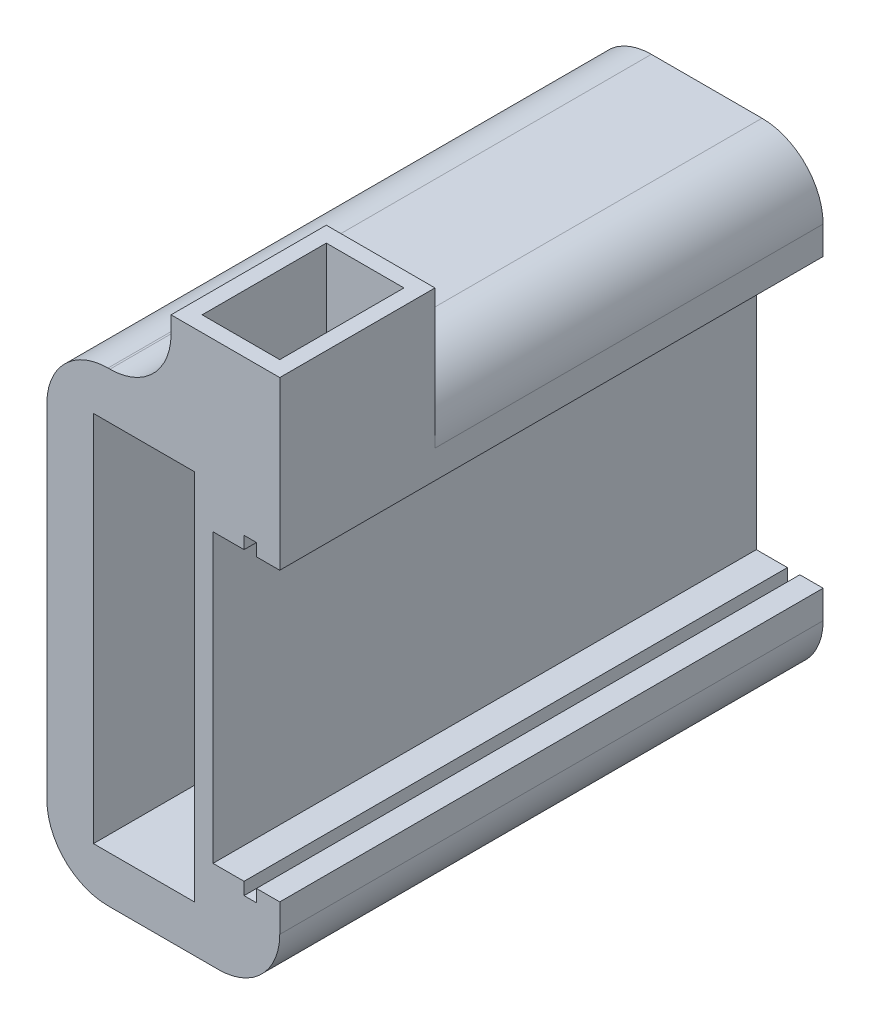
SolidWorks part; units mm, degrees
ref_plane "Front Plane" through (0, 0, 0) normal (0, 0, 1) x (1, 0, 0)
ref_plane "Top Plane" through (0, 0, 0) normal (0, 1, 0) x (1, 0, 0)
ref_plane "Right Plane" through (0, 0, 0) normal (1, 0, 0) x (0, 0, -1)
sketch "Sketch1" plane through (0, 0, 0) normal (0, 1, 0) x (1, 0, 0)
  line L1 (0, 0) -> (38.1, 0)
  line L2 (0, 0) -> (0, 88.9)
  line L3 (0, 88.9) -> (38.1, 88.9)
  line L4 (38.1, 0) -> (38.1, 88.9)
  dimension "D1" = 88.9
  dimension "D2" = 38.1
extrude "Boss-Extrude1" add sketch "Sketch1" along normal blind 76.2
sketch "Sketch2" plane through (0, 0, 0) normal (0, 0, 1) x (1, 0, 0)
  line L0 (0, 76.2) -> (0, 0) construction
  line L1 (7.62, 68.58) -> (24.13, 68.58)
  line L2 (7.62, 68.58) -> (7.62, 7.62)
  line L3 (7.62, 7.62) -> (24.13, 7.62)
  line L4 (24.13, 68.58) -> (24.13, 7.62)
  line L5 (0, 76.2) -> (38.1, 76.2) construction
  line L6 (0, 0) -> (38.1, 0) construction
  dimension "D1" = 7.62
  dimension "D2" = 7.62
  dimension "D3" = 7.62
  dimension "D4" = 16.51
extrude "Cut-Extrude1" cut sketch "Sketch2" against normal blind 76.2
sketch "Sketch3" plane through (0, 0, 0) normal (0, 0, 1) x (1, 0, 0)
  line L0 (38.1, 61.595) -> (24.13, 61.595)
  line L1 (34.29, 63.627) -> (32.258, 63.627)
  line L2 (34.29, 63.627) -> (34.29, 12.573)
  line L3 (34.29, 12.573) -> (32.258, 12.573)
  line L4 (32.258, 63.627) -> (32.258, 12.573)
  line L5 (38.1, 76.2) -> (38.1, 0) construction
  line L6 (24.13, 7.62) -> (24.13, 68.58) construction
  line L7 (38.1, 14.605) -> (24.13, 14.605)
  line L8 (24.13, 7.62) -> (24.13, 68.58) construction
  line L9 (27.178, 61.595) -> (27.178, 14.605)
  point P12 (32.258, 38.1)
  point P13 (24.13, 38.1)
  line M13 (38.1, 0) -> (38.1, 76.2)
  dimension "D1" = 51.054
  dimension "D2" = 2.032
  dimension "D3" = 2.032
  dimension "D4" = 2.032
  dimension "D5" = 3.81
  dimension "D6" = 5.08
extrude "Cut-Extrude2" cut sketch "Sketch3" against normal through all contours L0 L9 L7 L4 | L7 L2 L0 L4 | L7 L0 L2 M13 | L1 L4 L0 L2 | L2 L7 L4 L3 region at (36.195, 38.1, 0) region at (33.274, 38.1, 0) region at (33.274, 62.611, 0) region at (29.718, 38.1, 0) region at (33.274, 13.589, 0)
sketch "Sketch5" plane through (0, 76.2, 0) normal (0, 1, 0) x (1, 0, 0)
  line L3 (38.1, 0) -> (38.1, 88.9) construction
  line L4 (33.02, 2.54) -> (25.4, 2.54)
  line L5 (33.02, 2.54) -> (33.02, 15.24)
  line L6 (33.02, 15.24) -> (25.4, 15.24)
  line L7 (25.4, 2.54) -> (25.4, 15.24)
  line L8 (0, 0) -> (38.1, 0) construction
  dimension "D1" = 5.08
  dimension "D2" = 2.54
  dimension "D3" = 12.7
  dimension "D4" = 7.62
extrude "Cut-Extrude3" cut sketch "Sketch5" against normal up to surface (14.605 mm away) up to face at (29.718, 61.595, -44.45)
sketch "Sketch6" plane through (0, 76.2, 0) normal (0, 1, 0) x (1, 0, 0)
  line L0 (38.1, 0) -> (38.1, 88.9) construction
  line L1 (38.1, 0) -> (20.32, 0)
  line L2 (38.1, 0) -> (38.1, 25.4)
  line L3 (38.1, 25.4) -> (20.32, 25.4)
  line L4 (20.32, 0) -> (20.32, 25.4)
  line L5 (0, 0) -> (38.1, 0) construction
  line L7 (22.86, 22.86) -> (35.56, 22.86)
  line L8 (22.86, 22.86) -> (22.86, 2.54)
  line L9 (22.86, 2.54) -> (35.56, 2.54)
  line L10 (35.56, 22.86) -> (35.56, 2.54)
  dimension "D1" = 17.78
  dimension "D2" = 25.4
  dimension "D3" = 2.54
  dimension "D4" = 2.54
  dimension "D5" = 2.54
  dimension "D6" = 2.54
extrude "Boss-Extrude2" add sketch "Sketch6" along normal blind 12.7
fillet "Fillet2" radius 10 5 edges at (38.1, 76.2, -57.15) (20.32, 76.2, -12.7) (0, 76.2, -44.45) (0, 0, -44.45) (38.1, 0, -44.45)
sketch "Sketch7" plane through (0, 0, -88.9) normal (0, 0, -1) x (-1, 0, 0)
  line L0 (-27.178, 61.595) -> (0, 61.595) construction
  line L1 (0, 66.2) -> (0, 10) construction
  line L2 (-13.589, 63.5) -> (-13.589, 12.7) construction
  circle A0 centre (-13.589, 63.5) radius 2.7305
  circle A1 centre (-13.589, 12.7) radius 2.7305
  point P4 (-13.589, 61.595)
  point P5 (0, 38.1)
  point P6 (-13.589, 38.1)
  dimension "D1" = 5.461
  dimension "D2" = 5.461
  dimension "D3" = 50.8
extrude "Cut-Extrude4" cut sketch "Sketch7" against normal up to surface (12.7 mm away) up to face at (15.875, 38.1, -76.2)
